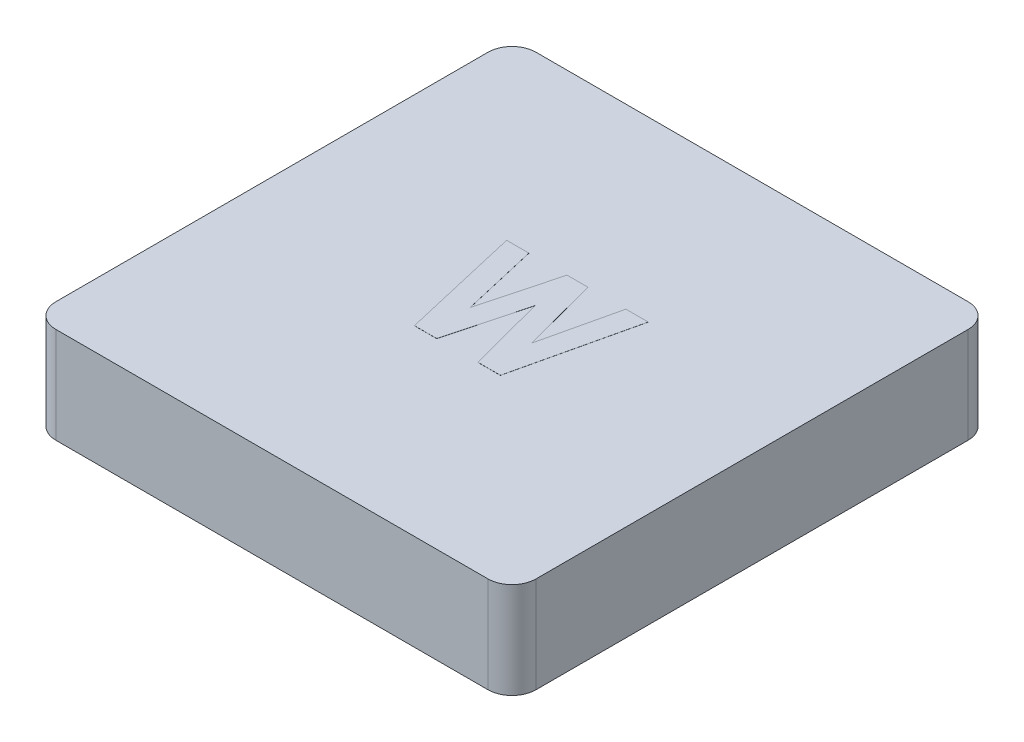
SolidWorks part; units mm, degrees
ref_plane "Front Plane" through (0, 0, 0) normal (0, 0, 1) x (1, 0, 0)
ref_plane "Top Plane" through (0, 0, 0) normal (0, 1, 0) x (1, 0, 0)
ref_plane "Right Plane" through (0, 0, 0) normal (1, 0, 0) x (0, 0, -1)
sketch "Sketch1" plane through (0, 0, 0) normal (0, 1, 0) x (1, 0, 0)
  line L0 (0, 0) -> (12.7, 0)
  line L1 (12.7, 0) -> (12.7, 12.7)
  line L2 (12.7, 12.7) -> (0, 12.7)
  line L3 (0, 12.7) -> (0, 0)
  dimension "D1" = 12.7
  dimension "D2" = 12.7
extrude "Boss-Extrude1" add sketch "Sketch1" along normal blind 2.54
fillet "Fillet1" radius 0.635 4 edges at (0, 1.27, -12.7) (12.7, 1.27, -12.7) (12.7, 1.27, 0) (0, 1.27, 0)
shell "Shell1" thickness 0.635 removed face at (6.35, 0, -6.35)
sketch "Sketch2" plane through (0, 1.905, 0) normal (0, -1, 0) x (-1, 0, 0)
  line L0 (-0.635, 6.35) -> (-12.065, 6.35) construction
  line L1 (-0.635, 12.065) -> (-0.635, 0.635) construction
  line L2 (-12.065, 0.635) -> (-12.065, 12.065) construction
  line L3 (-6.35, 0.635) -> (-6.35, 12.065) construction
  line L4 (-0.635, 0.635) -> (-12.065, 0.635) construction
  line L5 (-12.065, 12.065) -> (-0.635, 12.065) construction
  circle A0 centre (-6.35, 6.35) radius 2.54
  dimension "D1" = 5.08
extrude "Boss-Extrude2" add sketch "Sketch2" along normal up to surface (1.905 mm away) up to face at (6.35, 0, -6.35)
sketch "Sketch3" plane through (0, 2.54, 0) normal (0, 1, 0) x (1, 0, 0)
  line L0 (0, 12.065) -> (0, 0.635) construction
  line L1 (0.635, 0) -> (12.065, 0) construction
  text T0 "<b>W</b>"
  point P1 (0, 0)
  dimension "D1" = 4.4958
  dimension "D2" = 4.826
extrude "Boss-Extrude3" add sketch "Sketch3" along normal blind 0.0025
